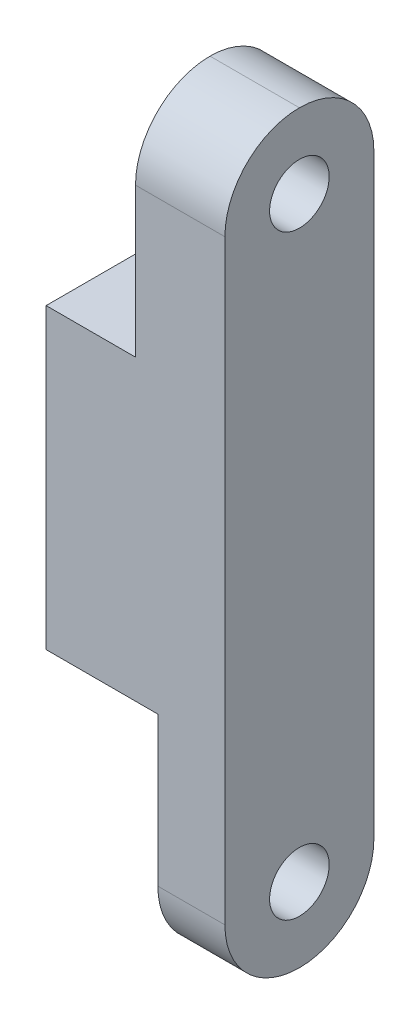
SolidWorks part; units mm, degrees
ref_plane "Front Plane" through (0, 0, 0) normal (0, 0, 1) x (1, 0, 0)
ref_plane "Top Plane" through (0, 0, 0) normal (0, 1, 0) x (1, 0, 0)
ref_plane "Right Plane" through (0, 0, 0) normal (1, 0, 0) x (0, 0, -1)
sketch "Sketch1" plane through (0, 0, 0) normal (0, 0, 1) x (1, 0, 0)
  line L1 (-6, 25) -> (6, 25)
  line L2 (-6, 25) -> (-6, -25)
  line L3 (-6, -25) -> (6, -25)
  line L4 (6, 25) -> (6, -25)
  dimension "D1" = 50
  dimension "D2" = 12
  dimension "D3" = 6
  dimension "D4" = 25
extrude "Boss-Extrude1" add sketch "Sketch1" along normal blind 10
sketch "Sketch2" plane through (0, 0, 10) normal (0, 0, 1) x (1, 0, 0)
  line L0 (6, 25) -> (-6, 25) construction
  line L1 (-6, -25) -> (1.5, -25)
  line L2 (-6, -25) -> (-6, -10)
  line L3 (-6, -10) -> (1.5, -10)
  line L4 (1.5, -25) -> (1.5, -10)
  line L5 (0, 25) -> (-6, 25)
  line L6 (0, 25) -> (0, 10)
  line L7 (0, 10) -> (-6, 10)
  line L8 (-6, 25) -> (-6, 10)
  line L9 (-6, 25) -> (-6, -25) construction
  dimension "D1" = 15
  dimension "D2" = 15
  dimension "D3" = 7.5
extrude "Cut-Extrude1" cut sketch "Sketch2" against normal blind 10
sketch "Sketch3" plane through (0, 0, 0) normal (-1, 0, 0) x (0, 0, 1)
  line L0 (10, 10) -> (10, 25) construction
  line L1 (0, 25) -> (10, 25) construction
  line L2 (-6.0544, 0) -> (16.1996, 0) construction
  circle A0 centre (5, 20) radius 2
  circle A1 centre (5, -20) radius 2
  dimension "D2" = 4
  dimension "D1" = 5
  dimension "D3" = 5
extrude "Cut-Extrude2" cut sketch "Sketch3" against normal blind 10
fillet "Fillet1" radius 5 4 edges at (3.75, -25, 0) (3.75, -25, 10) (3, 25, 0) (3, 25, 10)
equation "\"D3@Sketch1\"=\"D2@Sketch1\"/2"
